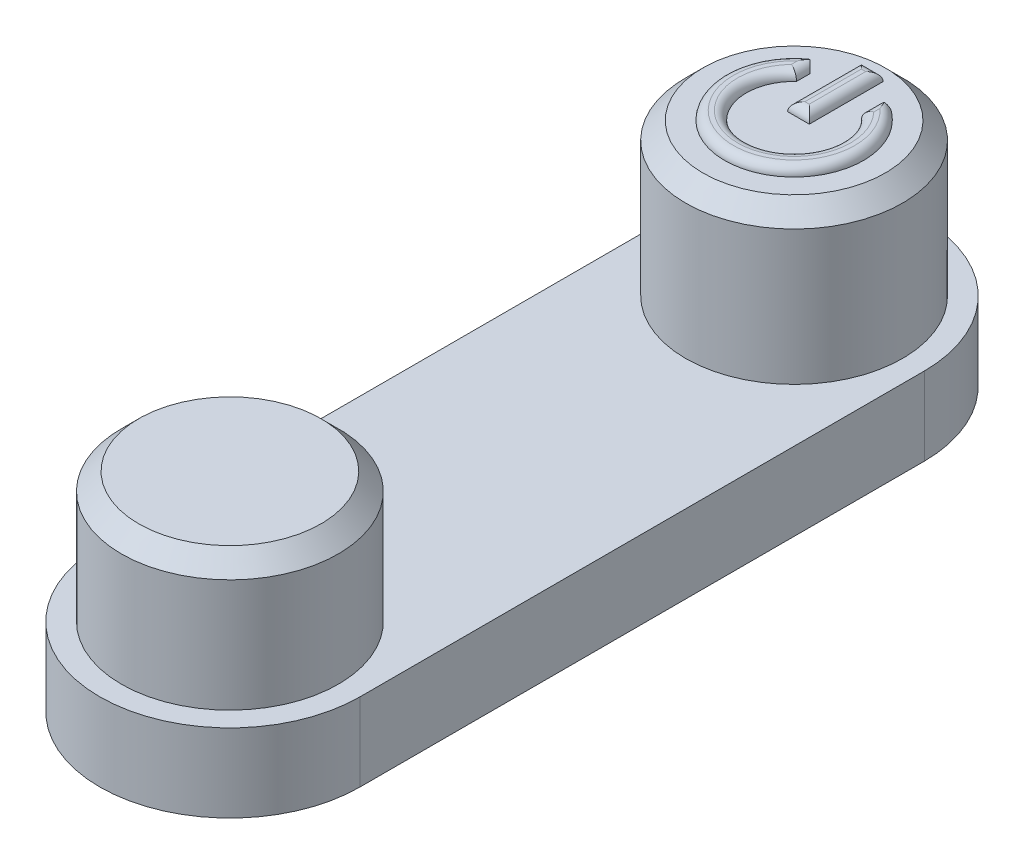
SolidWorks part; units mm, degrees
ref_plane "Front Plane" through (0, 0, 0) normal (0, 0, 1) x (1, 0, 0)
ref_plane "Top Plane" through (0, 0, 0) normal (0, 1, 0) x (1, 0, 0)
ref_plane "Right Plane" through (0, 0, 0) normal (1, 0, 0) x (0, 0, -1)
sketch "Sketch1" plane through (0, 0, 0) normal (0, 1, 0) x (1, 0, 0)
  line L0 (0, -6.5) -> (0, 6.5) construction
  line L1 (-3, -6.5) -> (-3, 6.5)
  line L2 (3, -6.5) -> (3, 6.5)
  arc A0 (-3, -6.5) -> (3, -6.5) centre (0, -6.5) ccw
  arc A1 (3, 6.5) -> (-3, 6.5) centre (0, 6.5) ccw
  point P2 (0, 0)
  dimension "D1" = 13
  dimension "D2" = 6
extrude "Boss-Extrude1" add sketch "Sketch1" along normal blind 1.8
sketch "Sketch2" plane through (0, 1.8, 0) normal (0, 1, 0) x (1, 0, 0)
  circle A0 centre (0, 6.5) radius 2.5
  circle A1 centre (0, -6.5) radius 2.5
  dimension "D1" = 5
extrude "Boss-Extrude2" add sketch "Sketch2" along normal blind 3
sketch "Sketch3" plane through (0, 4.8, 0) normal (0, 1, 0) x (1, 0, 0)
  circle A1 centre (0, 6.5) radius 2.5
  circle A2 centre (0, 6.5) radius 2.5
  dimension "D1" = 0
extrude "Boss-Extrude3" add sketch "Sketch3" along normal blind 0.5
chamfer "Chamfer1" distance 0.4 angle 45 2 edges at (0, 4.8, 9) (0, 5.3, -4)
sketch "Sketch4" plane through (0, 5.3, 0) normal (0, 1, 0) x (1, 0, 0)
  line L0 (0, 6.5) -> (0, 8.1) construction
  line L1 (-0.75, 7.9133) -> (-0.75, 7.3047)
  line L2 (0.75, 7.9133) -> (0.75, 7.3047)
  line L4 (-0.25, 6.6) -> (0.25, 6.6)
  line L5 (-0.25, 6.6) -> (-0.25, 8.3)
  line L6 (-0.25, 8.3) -> (0.25, 8.3)
  line L7 (0.25, 6.6) -> (0.25, 8.3)
  line L8 (-0.25, 6.6) -> (0.25, 8.3) construction
  line L9 (-0.25, 8.3) -> (0.25, 6.6) construction
  arc A0 (-0.75, 7.9133) -> (0.75, 7.9133) centre (0, 6.5) ccw
  arc A1 (-0.75, 7.3047) -> (0.75, 7.3047) centre (0, 6.5) ccw
  arc A2 (0, 7.6) -> (-0.75, 7.3047) centre (0, 6.5) ccw construction
  arc A3 (0.75, 7.3047) -> (0, 7.6) centre (0, 6.5) ccw construction
  arc A4 (0.75, 7.9133) -> (0, 8.1) centre (0, 6.5) ccw construction
  arc A5 (0, 8.1) -> (-0.75, 7.9133) centre (0, 6.5) ccw construction
  point P1 (0, 7.45)
  dimension "D1" = 1.6
  dimension "D2" = 0.5
  dimension "D3" = 1.5
  dimension "D4" = 0.5
  dimension "D5" = 1.7
  dimension "D6" = 1.8
extrude "Boss-Extrude4" add sketch "Sketch4" along normal blind 0.2
chamfer "Chamfer2" distance 0.3 angle 45 2 edges at (0.75, 5.4, -7.9133) (-0.75, 5.4, -7.9133) first distance on face at (0, 5.4, -6.4067) first distance on face at (-0.75, 5.4, -7.609)
fillet "Fillet1" radius 0.2 8 edges at (0, 5.5, -6.6) (-0.25, 5.5, -7.45) (0, 5.5, -8.3) (0.25, 5.5, -7.45) (-0.75, 5.5, -7.459) (0, 5.5, -5.4) (0.75, 5.5, -7.4981) (-0.0297, 5.5, -4.9003)
